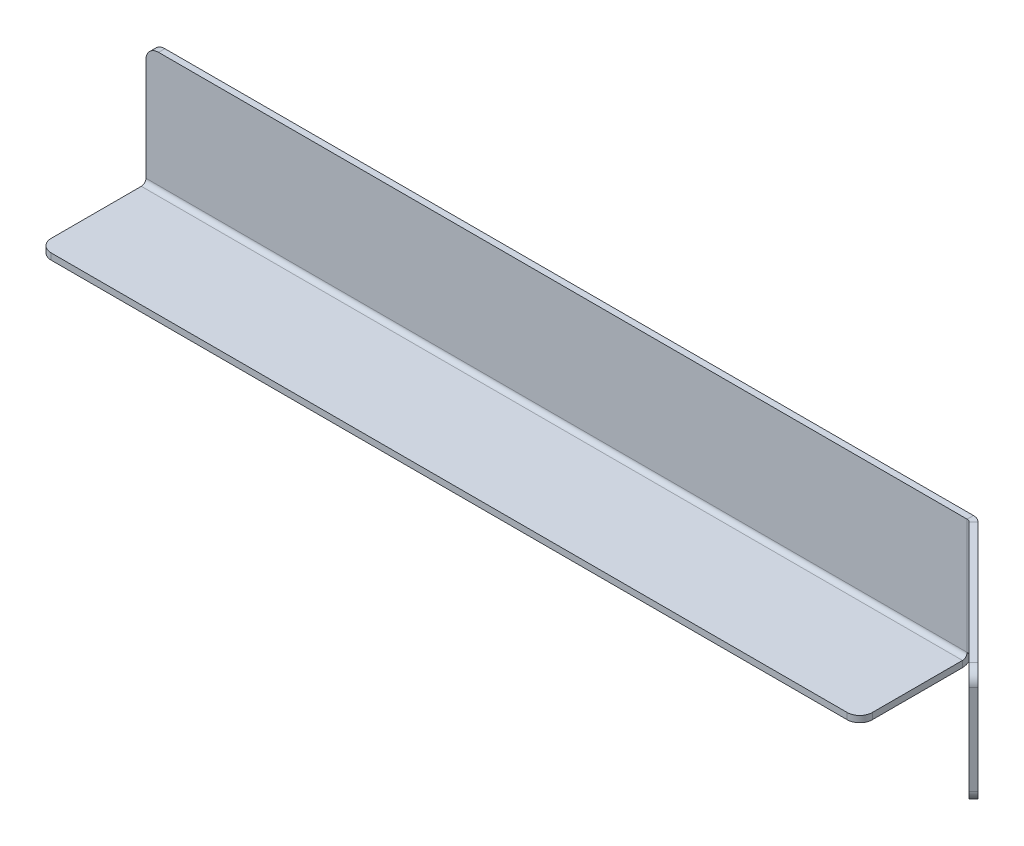
SolidWorks part; units mm, degrees
note: The reader was unsure of these and kept them because the rebuilt part matched: flange length of "Edge-Flange1", "Edge-Flange2".
ref_plane "Front Plane" through (0, 0, 0) normal (0, 0, 1) x (1, 0, 0)
ref_plane "Top Plane" through (0, 0, 0) normal (0, 1, 0) x (1, 0, 0)
ref_plane "Right Plane" through (0, 0, 0) normal (1, 0, 0) x (0, 0, -1)
sketch "Sketch2" plane through (0, 0, 0) normal (0, 0, 1) x (1, 0, 0)
  line L1 (0, 0) -> (-130, 0)
  line L2 (0, 0) -> (0, 20)
  line L3 (0, 20) -> (-130, 20)
  line L4 (-130, 0) -> (-130, 20)
  dimension "D1" = 20
  dimension "D2" = 130
base flange "Base-Flange1" sketch "Sketch2" thickness 1 reverse thickness direction no parameters "D1"=0.7366
ref_plane "Plane1" through (0, 0, 0) normal (1, 0, 0) x (0, 0, -1)
edge flange "Edge-Flange1" sketch "Sketch10" flange angle 90 flange length 18 flange position material inside bend radius 0.7366 thickness 1 relief rectangular parameters "D6"=10
sketch "Sketch10" plane through (0, 0, 0) normal (0, -1, 0) x (1, 0, 0)
  line L2 (-130, 0) -> (-130, 17)
  line L3 (-130, 17) -> (0, 17)
  line L4 (0, 17) -> (0, 0)
  line L9 (-130, 0) -> (0, 0) construction
  line L10 (-130, 0) -> (0, 0)
bend "EdgeBend1" bend radius 0.7366 bend angle 90 parameters "D5"=1
edge flange "Edge-Flange2" sketch "Sketch14" flange angle 135 flange length 30 flange position bend outside bend radius 0.7366 thickness 1 relief rectangular parameters "D6"=10
sketch "Sketch14" plane through (0, 0, 0) normal (0.7071, 0, -0.7071) x (0, 1, 0)
  line L2 (1.7366, 0) -> (1.7366, 29.5858)
  line L3 (1.7366, 29.5858) -> (20, 29.5858)
  line L4 (20, 29.5858) -> (20, 0)
  line L7 (1.7366, 0) -> (20, 0) construction
  line L9 (1.7366, 0) -> (20, 0)
bend "EdgeBend2" bend radius 0.7366 bend angle 45 parameters "D5"=2
fillet "Fillet1" radius 2 5 edges at (0, 0.5, 17) (-130, 0.5, 17) (-130, 20, -0.5) (21.579, 1.7366, 20.5668) (21.579, 20, 20.5668)
sketch "Bend-Lines1" [suppressed] plane through (0, 0, 0) normal (0, 1, 0) x (1, 0, 0)
sketch "Bounding-Box1" [suppressed] plane through (0, 0, 0) normal (0, 1, 0) x (1, 0, 0)
sheet metal parameters "Sheet-Metal1" thickness 1 parameters "D1"=0.7366
flat pattern "Flat-Pattern1" [suppressed]
sketch "Bend-Lines2" plane through (0, 0, 0) normal (0, 1, 0) x (1, 0, 0)
sketch3d "Bounding-Box2" [suppressed]
  line L0 (64.5873, 0, 0) -> (0, 0, 0) construction
  line L1 (64.5873, 22.0538, 0) -> (0, 22.0538, 0) construction
  line L2 (64.5873, 0, 0) -> (64.5873, 22.0538, 0) construction
  line L3 (0, 0, 0) -> (0, 22.0538, 0) construction
sheet metal parameters "Sheet-Metal2" thickness 1 parameters "D1"=0.7366
flat pattern "Flat-Pattern1"
sketch "Bend-Lines2" plane through (0, 0, 0) normal (0, 0, 1) x (1, 0, 0)
  line L0 (-64.5873, 0.7654) -> (0, 0.7654) construction
  line L1 (-64.5873, 0.7654) -> (0, 0.7654) construction
sketch3d "Bounding-Box2" [suppressed]
  line L0 (-64.5873, -7.4692, 0) -> (0, -7.4692, 0) construction
  line L1 (-64.5873, 22.0538, 0) -> (0, 22.0538, 0) construction
  line L2 (-64.5873, -7.4692, 0) -> (-64.5873, 22.0538, 0) construction
  line L3 (0, -7.4692, 0) -> (0, 22.0538, 0) construction
bend of the flat pattern "Flatten-<EdgeBend1>1"
sheet metal parameters "Sheet-Metal3" thickness 1 parameters "D1"=0.7366
flat pattern "Flat-Pattern1"
sketch "Bend-Lines2" plane through (0, 0, 0) normal (0, 0, 1) x (1, 0, 0)
  line L0 (-130, 0.7654) -> (0, 0.7654) construction
  line L1 (-130, 0.7654) -> (0, 0.7654) construction
  line L2 (0.4856, 1.7366) -> (0.4856, 20) construction
  line L3 (0.4856, 1.7366) -> (0.4856, 20) construction
sketch3d "Bounding-Box2" [suppressed]
  line L0 (-130, -16.4692, 0) -> (30.2519, -16.4692, 0) construction
  line L1 (-130, 20, 0) -> (30.2519, 20, 0) construction
  line L2 (-130, -16.4692, 0) -> (-130, 20, 0) construction
  line L3 (30.2519, -16.4692, 0) -> (30.2519, 20, 0) construction
bend of the flat pattern "Flatten-<EdgeBend2>1"
bend of the flat pattern "Flatten-<EdgeBend1>1"
